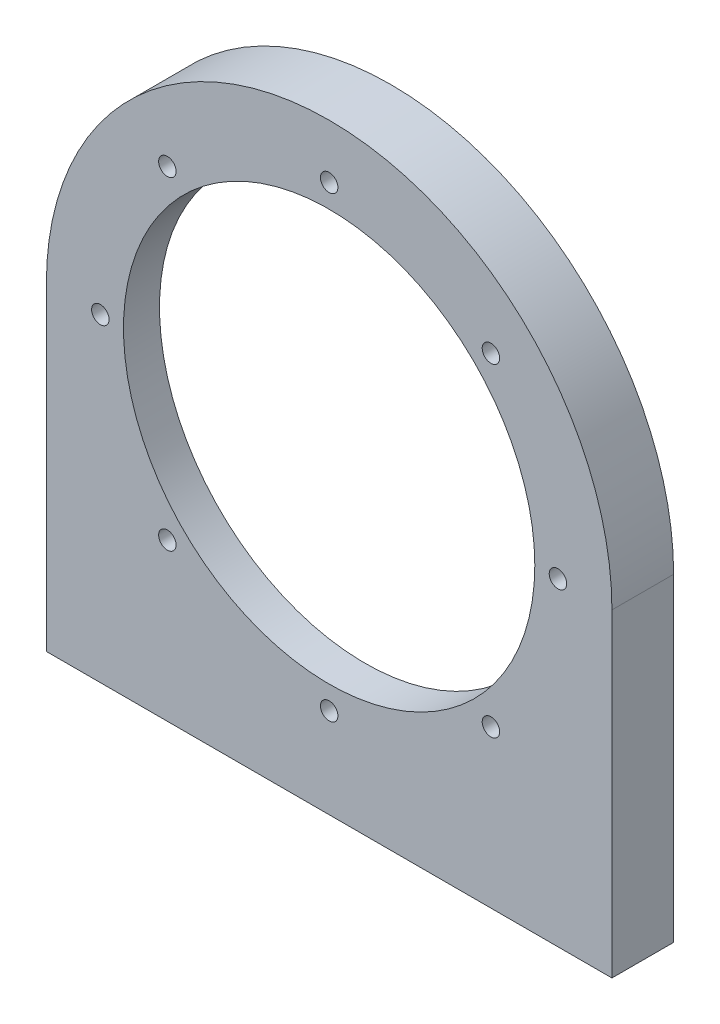
SolidWorks part; units mm, degrees
material "6063-T6"
ref_plane "Front Plane" through (0, 0, 0) normal (0, 0, 1) x (1, 0, 0)
ref_plane "Top Plane" through (0, 0, 0) normal (0, 1, 0) x (1, 0, 0)
ref_plane "Right Plane" through (0, 0, 0) normal (1, 0, 0) x (0, 0, -1)
sketch "Sketch1" plane through (0, 0, 0) normal (0, 0, 1) x (1, 0, 0)
  circle A0 centre (0, 0) radius 55
  circle A1 centre (0, 0) radius 40
  dimension "D1" = 110
  dimension "D2" = 80
extrude "Boss-Extrude1" add sketch "Sketch1" along normal blind 7
sketch "Sketch2" plane through (0, 0, 7) normal (0, 0, 1) x (1, 0, 0)
  circle A0 centre (0, 0) radius 44.5 construction
  point P5 (0, 44.5)
  point P13 (31.4663, 31.4663)
  point P14 (44.5, 0)
  point P15 (31.4663, -31.4663)
  point P16 (0, -44.5)
  point P17 (-31.4663, -31.4663)
  point P18 (-44.5, 0)
  point P19 (-31.4663, 31.4663)
  dimension "D1" = 89
  dimension "D2" = 8
hole_wizard "M3 Clearance Hole1" positions "Sketch2" profile "Sketch3" hole size "M3" standard "DIN" end condition through all
sketch "Sketch3" plane through (-31.4663, 31.4663, 7) normal (1, 0, 0) x (0, -1, 0)
  line L0 (0, 0) -> (0, 7)
  line L1 (0, 7) -> (1.7, 7)
  line L2 (1.7, 7) -> (1.7, 0)
  line L5 (1.7, 0) -> (0, 0)
  line L11 (0, -6.35) -> (0, 107.95) construction
  dimension "Thru Hole Dia." = 3.4
  dimension "Thru Hole Depth" = 7
sketch "Sketch4" plane through (0, 0, 0) normal (0, 0, -1) x (-1, 0, 0)
  circle A0 centre (0, 0) radius 50
  circle A1 centre (0, 0) radius 55 construction
  circle A2 centre (0, 0) radius 55
  dimension "D1" = 100
extrude "Boss-Extrude3" add sketch "Sketch4" along normal blind 5
sketch "Sketch5" plane through (0, 0, 7) normal (0, 0, 1) x (1, 0, 0)
  line L0 (-55, 0) -> (-55, -62)
  line L1 (-55, -62) -> (55, -62)
  line L2 (55, -62) -> (55, 0)
  circle A0 centre (0, 0) radius 55 construction
  arc A1 (-55, 0) -> (55, 0) centre (0, 0) ccw
  dimension "D1" = 62
extrude "Boss-Extrude4" add sketch "Sketch5" against normal up to surface (12 mm away) up to face at (-55, 0, -5)
sketch "Sketch7" plane through (0, -62, 0) normal (0, -1, 0) x (-1, 0, 0)
  line L0 (-55, -1) -> (55, -1) construction
  line L1 (-55, 5) -> (-55, -7) construction
  line L2 (55, 5) -> (55, -7) construction
  point P9 (0, -1)
  point P19 (25, -1)
  point P20 (50, -1)
  point P21 (0, -1)
  point P22 (25, -1)
  point P23 (-25, -1)
  point P24 (0, -1)
  point P25 (-25, -1)
  point P26 (-50, -1)
  dimension "D1" = 3
  dimension "D2" = 3
hole_wizard "Tap Drill for M4 Tap1" positions "Sketch7" profile "Sketch8" hole size "M4" standard "DIN"
sketch "Sketch8" plane through (50, -62, 1) normal (1, 0, 0) x (0, 0, -1)
  line L0 (0, 0) -> (0, 10.9914)
  line L1 (0, 10.9914) -> (1.65, 10)
  line L2 (1.65, 10) -> (1.65, 0)
  line L5 (1.65, 0) -> (0, 0)
  line L10 (0, 10.9914) -> (-1.65, 10) construction
  line L11 (0, -6.35) -> (0, 107.95) construction
  dimension "Hole Dia." = 3.3
  dimension "Hole Depth" = 10
  dimension "Drill Angle" = 118
